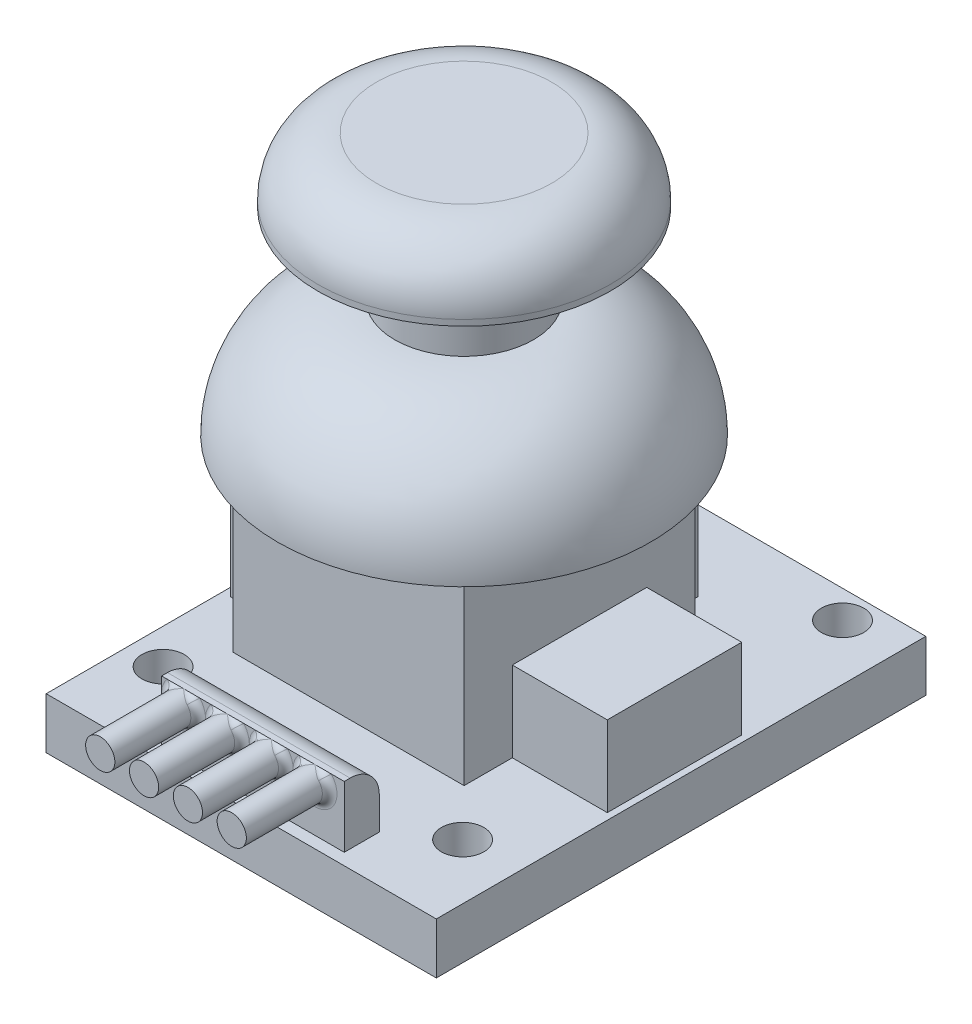
SolidWorks part; units mm, degrees
ref_plane "Спереди" through (0, 0, 0) normal (0, 0, 1) x (1, 0, 0)
ref_plane "Сверху" through (0, 0, 0) normal (0, 1, 0) x (1, 0, 0)
ref_plane "Справа" through (0, 0, 0) normal (1, 0, 0) x (0, 0, -1)
sketch "Sketch1" plane through (0, 0, 0) normal (0, 1, 0) x (1, 0, 0)
  line L1 (13.35, -16.75) -> (-13.35, -16.75)
  line L2 (13.35, -16.75) -> (13.35, 16.75)
  line L3 (13.35, 16.75) -> (-13.35, 16.75)
  line L4 (-13.35, -16.75) -> (-13.35, 16.75)
  line L5 (13.35, -16.75) -> (-13.35, 16.75) construction
  line L6 (13.35, 16.75) -> (-13.35, -16.75) construction
  point P0 (0, 0)
  dimension "D1" = 26.7
  dimension "D2" = 33.5
extrude "Boss-Extrude1" add sketch "Sketch1" along normal blind 3.5
sketch "Sketch2" plane through (0, 3.5, 0) normal (0, 1, 0) x (1, 0, 0)
  line L0 (13.35, 0) -> (-13.35, 0) construction
  line L1 (6.4, -7.9) -> (-9.4, -7.9)
  line L2 (6.4, -7.9) -> (6.4, 7.9)
  line L3 (6.4, 7.9) -> (-9.4, 7.9)
  line L4 (-9.4, -7.9) -> (-9.4, 7.9)
  line L5 (6.4, -7.9) -> (-9.4, 7.9) construction
  line L6 (6.4, 7.9) -> (-9.4, -7.9) construction
  line L7 (13.35, -16.75) -> (13.35, 16.75) construction
  line L8 (-13.35, 16.75) -> (-13.35, -16.75) construction
  point P0 (-1.5, 0)
  dimension "D1" = 15.8
  dimension "D2" = 1.5
extrude "Boss-Extrude2" add sketch "Sketch2" along normal blind 12.9
sketch "Sketch3" plane through (0, 16.4, 0) normal (0, 1, 0) x (1, 0, 0)
  circle A0 centre (0, 0) radius 1.9
  dimension "D1" = 3.8
extrude "Boss-Extrude3" add sketch "Sketch3" along normal blind 6.9
sketch "Sketch4" plane through (-9.4, 0, 0) normal (-1, 0, 0) x (0, 0, 1)
  line L0 (0, 16.4) -> (0, 3.5) construction
  line L1 (-7.9, 16.4) -> (7.9, 16.4) construction
  line L2 (-7.9, 3.5) -> (7.9, 3.5) construction
  line L4 (4.7, 3.5) -> (-4.7, 3.5)
  line L5 (4.7, 3.5) -> (4.7, 16.4)
  line L6 (4.7, 16.4) -> (-4.7, 16.4)
  line L7 (-4.7, 3.5) -> (-4.7, 16.4)
  line L8 (4.7, 3.5) -> (-4.7, 16.4) construction
  line L9 (4.7, 16.4) -> (-4.7, 3.5) construction
  point P6 (0, 9.95)
  dimension "D1" = 9.4
extrude "Boss-Extrude4" add sketch "Sketch4" along normal blind 3.4
sketch "Sketch5" plane through (0, 0, -7.9) normal (0, 0, -1) x (-1, 0, 0)
  line L0 (1.5, 16.4) -> (1.5, 3.5) construction
  line L1 (-6.4, 16.4) -> (9.4, 16.4) construction
  line L2 (-6.4, 3.5) -> (9.4, 3.5) construction
  line L4 (-3.2, 3.5) -> (6.2, 3.5)
  line L5 (-3.2, 3.5) -> (-3.2, 16.4)
  line L6 (-3.2, 16.4) -> (6.2, 16.4)
  line L7 (6.2, 3.5) -> (6.2, 16.4)
  line L8 (-3.2, 3.5) -> (6.2, 16.4) construction
  line L9 (-3.2, 16.4) -> (6.2, 3.5) construction
  point P6 (1.5, 9.95)
  dimension "D1" = 9.4
extrude "Boss-Extrude5" add sketch "Sketch5" along normal blind 3.4
sketch "Sketch6" plane through (6.4, 0, 0) normal (1, 0, 0) x (0, 0, -1)
  line L0 (0, 16.4) -> (0, 3.5) construction
  line L1 (-7.9, 16.4) -> (7.9, 16.4) construction
  line L2 (-7.9, 3.5) -> (7.9, 3.5) construction
  line L4 (-4.6, 9) -> (4.6, 9)
  line L5 (-4.6, 9) -> (-4.6, 3.5)
  line L6 (-4.6, 3.5) -> (4.6, 3.5)
  line L7 (4.6, 9) -> (4.6, 3.5)
  line L8 (-4.6, 9) -> (4.6, 3.5) construction
  line L9 (-4.6, 3.5) -> (4.6, 9) construction
  point P6 (0, 6.25)
  dimension "D1" = 9.2
  dimension "D2" = 5.5
extrude "Boss-Extrude6" add sketch "Sketch6" along normal blind 6.5
sketch "Sketch8" plane through (0, 16.4, 0) normal (0, 1, 0) x (1, 0, 0)
  line L0 (6.4, 7.9) -> (-9.4, -7.9) construction
  circle A0 centre (-1.5, 0) radius 12.75
  point P8 (-1.5, 0)
  dimension "D1" = 25.5
extrude "Boss-Extrude7" add sketch "Sketch8" along normal blind 8
fillet "Fillet1" radius 8 1 edges at (-1.5, 24.4, 12.75)
sketch "Sketch9" plane through (0, 24.4, 0) normal (0, 1, 0) x (1, 0, 0)
  circle A0 centre (-1.5, 0) radius 4.75
extrude "Boss-Extrude8" add sketch "Sketch9" along normal blind 5.5
sketch "Sketch10" plane through (0, 29.9, 0) normal (0, 1, 0) x (1, 0, 0)
  circle A0 centre (-1.5, 0) radius 10
  dimension "D1" = 20
extrude "Boss-Extrude9" add sketch "Sketch10" along normal blind 4.4
fillet "Fillet2" radius 4 1 edges at (-1.5, 34.3, 10)
sketch "Sketch11" plane through (0, 3.5, 0) normal (0, 1, 0) x (1, 0, 0)
  line L0 (-13.35, -14.75) -> (13.35, -14.75) construction
  line L1 (-13.35, 16.75) -> (-13.35, -16.75) construction
  line L2 (13.35, -16.75) -> (13.35, 16.75) construction
  line L3 (-13.35, -16.75) -> (13.35, -16.75) construction
  line L5 (6.25, -15.95) -> (-6.25, -15.95)
  line L6 (6.25, -15.95) -> (6.25, -13.55)
  line L7 (6.25, -13.55) -> (-6.25, -13.55)
  line L8 (-6.25, -15.95) -> (-6.25, -13.55)
  line L9 (6.25, -15.95) -> (-6.25, -13.55) construction
  line L10 (6.25, -13.55) -> (-6.25, -15.95) construction
  point P8 (0, -14.75)
  dimension "D1" = 2
  dimension "D2" = 2.4
  dimension "D3" = 12.5
extrude "Boss-Extrude10" add sketch "Sketch11" along normal blind 4.2
sketch "Sketch12" plane through (0, 0, 15.95) normal (0, 0, 1) x (1, 0, 0)
  line L0 (-6.25, 6.7) -> (6.25, 6.7) construction
  line L1 (-6.25, 7.7) -> (-6.25, 3.5) construction
  line L2 (6.25, 7.7) -> (6.25, 3.5) construction
  circle A0 centre (-4.75, 6.7) radius 1
  circle A1 centre (-1.75, 6.7) radius 1
  circle A2 centre (1.25, 6.7) radius 1
  circle A3 centre (4.25, 6.7) radius 1
  dimension "D1" = 1
  dimension "D2" = 3
  dimension "D3" = 3
  dimension "D4" = 3
  dimension "D5" = 1.5
extrude "Boss-Extrude11" add sketch "Sketch12" along normal blind 5.7
fillet "Fillet3" radius 2 1 edges at (0, 7.7, 13.55)
fillet "Fillet4" radius 0.5 4 edges at (5.25, 6.7, 15.95) (2.25, 6.7, 15.95) (-0.75, 6.7, 15.95) (-3.75, 6.7, 15.95)
sketch "Sketch13" plane through (0, 0, 0) normal (0, -1, 0) x (1, 0, 0)
  line L0 (9.55, -14.85) -> (-10.95, -14.85) construction
  line L1 (-10.95, -14.85) -> (-10.95, 11.15) construction
  line L2 (-10.95, 11.15) -> (9.55, 11.15) construction
  line L3 (9.55, 11.15) -> (9.55, -14.85) construction
  line L4 (13.35, -16.75) -> (-13.35, -16.75) construction
  line L5 (-13.35, -16.75) -> (-13.35, 16.75) construction
  circle A0 centre (9.55, -14.85) radius 1.45
  circle A2 centre (-10.95, 11.15) radius 1.45
  circle A3 centre (9.55, 11.15) radius 1.45
  dimension "D1" = 2.9
  dimension "D2" = 20.5
  dimension "D3" = 26
  dimension "D4" = 1.9
  dimension "D5" = 2.4
extrude "Cut-Extrude1" cut sketch "Sketch13" against normal up to next
sketch "Sketch14" plane through (0, 3.5, 0) normal (0, 1, 0) x (1, 0, 0)
  line L0 (-13.35, 13.2145) -> (-9.8145, 16.75)
  line L1 (-13.35, 16.75) -> (-13.35, -16.75) construction
  line L2 (13.35, 16.75) -> (-13.35, 16.75) construction
  line L3 (-9.8145, 16.75) -> (-13.35, 16.75)
  line L4 (-13.35, 16.75) -> (-13.35, 13.2145)
  dimension "D1" = 45
  dimension "D2" = 5
extrude "Cut-Extrude2" cut sketch "Sketch14" against normal through all
